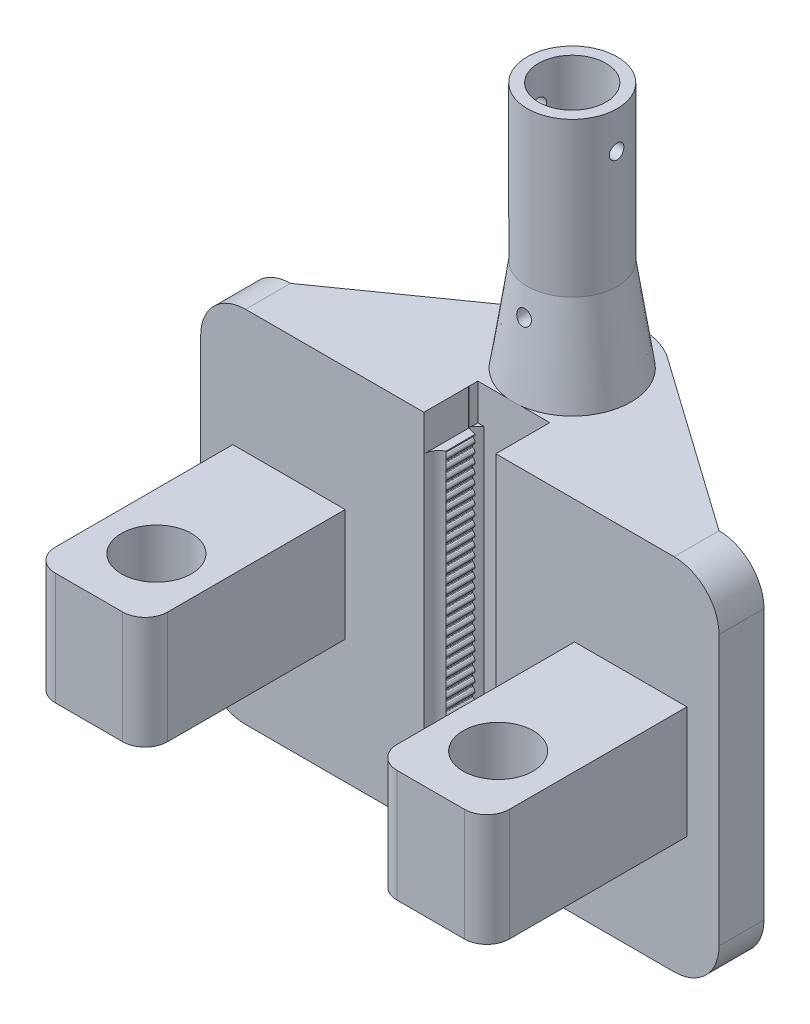
SolidWorks part; units mm, degrees
ref_plane "Piano frontale" through (0, 0, 0) normal (0, 0, 1) x (1, 0, 0)
ref_plane "Piano superiore" through (0, 0, 0) normal (0, 1, 0) x (1, 0, 0)
ref_plane "Piano destro" through (0, 0, 0) normal (1, 0, 0) x (0, 0, -1)
sketch "Schizzo1" plane through (0, 0, 0) normal (0, 0, 1) x (1, 0, 0)
  line L1 (-57.665, 40) -> (57.665, 40)
  line L2 (-57.665, 40) -> (-57.665, -40)
  line L3 (-57.665, -40) -> (57.665, -40)
  line L4 (57.665, 40) -> (57.665, -40)
  line L5 (-57.665, 40) -> (57.665, -40) construction
  line L6 (-57.665, -40) -> (57.665, 40) construction
  point P0 (0, 0)
  dimension "D1" = 80
  dimension "D2" = 115.33
extrude "Estrusione-Estrusione1" add sketch "Schizzo1" along normal blind 10
fillet "Raccordo1" radius 10 4 edges at (-57.665, -40, 5) (57.665, -40, 5) (57.665, 40, 5) (-57.665, 40, 5)
sketch "Schizzo2" plane through (0, 0, 10) normal (0, 0, 1) x (1, 0, 0)
  line L1 (-6.11, 27.5) -> (6.11, 27.5)
  line L2 (-6.11, 27.5) -> (-6.11, -27.5)
  line L3 (-6.11, -27.5) -> (6.11, -27.5)
  line L4 (6.11, 27.5) -> (6.11, -27.5)
  line L5 (-6.11, 27.5) -> (6.11, -27.5) construction
  line L6 (-6.11, -27.5) -> (6.11, 27.5) construction
  point P0 (0, 0)
  dimension "D1" = 55
  dimension "D2" = 12.22
extrude "Estrusione-Estrusione2" add sketch "Schizzo2" against normal blind 5 contours L1 L4 L3 L2
sketch "Schizzo6" plane through (0, 0, 10) normal (0, 0, 1) x (1, 0, 0)
  line L0 (0, 0) -> (49.9303, 0) construction
  line L2 (-6.11, 21.3859) -> (-6.11, -21.3859)
  line L4 (6.11, 21.3859) -> (6.11, -21.3859)
  line L5 (-6.11, 27.5) -> (6.11, -27.5) construction
  line L6 (-6.11, -27.5) -> (6.11, 27.5) construction
  arc A1 (6.11, -21.3859) -> (-6.11, -21.3859) centre (0, -21.3859) cw
  arc A2 (6.11, 21.3859) -> (-6.11, 21.3859) centre (0, 21.3859) ccw
  point P0 (0, 0)
  dimension "D1" = 12.22
  dimension "D2" = 55
extrude "Taglio-Estrusione6" cut sketch "Schizzo6" against normal blind 7
sketch "Schizzo9" plane through (0, 0, 0) normal (0, 0, -1) x (-1, 0, 0)
  line L0 (0, 0) -> (-26.4048, 0) construction
  line L1 (6.11, 23.4312) -> (6.11, -23.4312)
  line L2 (-6.11, 23.4312) -> (-6.11, -23.4312)
  line L3 (6.11, 23.4312) -> (6.11, 40)
  line L4 (-47.665, 40) -> (47.665, 40) construction
  line L5 (6.11, 40) -> (-6.11, 40)
  line L6 (-6.11, 40) -> (-6.11, 23.4312)
  arc A5 (-6.11, -23.4312) -> (6.11, -23.4312) centre (0, -23.4312) ccw
  point P0 (0, 0)
extrude "Taglio-Estrusione8" cut sketch "Schizzo9" against normal blind 53 contours A5 L1 L3 L5 L6 L2
ref_plane "Piano1" through (0, 95, 0) normal (0, 1, 0) x (1, 0, 0)
sketch "Schizzo14" plane through (0, 95, 0) normal (0, 1, 0) x (1, 0, 0)
  circle A1 centre (0, 15) radius 10
  dimension "D2" = 20
extrude "Estrusione-Estrusione5" add sketch "Schizzo14" against normal blind 135 separate body
ref_plane "Piano2" through (0, 0, 5) normal (0, 0, 1) x (1, 0, 0)
ref_plane "Piano3" through (0, -40, 0) normal (0, 1, 0) x (1, 0, 0)
sketch "Schizzo20" plane through (0, -40, 0) normal (0, 1, 0) x (1, 0, 0)
  line L0 (-13.0862, 15) -> (-13.0862, 0)
  line L1 (-47.665, 0) -> (47.665, 0) construction
  line L2 (-13.0862, 0) -> (13.0862, 0)
  line L3 (13.0862, 0) -> (13.0862, 15)
  arc A0 (13.0862, 15) -> (-13.0862, 15) centre (0, 15) ccw
chamfer "Smusso1" distance 2 angle 15 3 edges at (-6.11, 8.2844, 0) (6.11, 8.2844, 0) (0, -29.5412, 0) first distance on face at (0, 2.2523, 0)
ref_plane "Piano4" through (0, 0, 7) normal (0, 0, 1) x (1, 0, 0)
sketch "Schizzo22" plane through (0, 0, 7) normal (0, 0, 1) x (1, 0, 0)
  line L0 (0, 0) -> (47.566, 0) construction
  line L1 (-8, 23.4312) -> (-8, -23.4312)
  line L2 (8, 23.4312) -> (8, -23.4312)
  line L3 (-8, 23.4312) -> (-8, 40)
  line L4 (47.665, 40) -> (6.11, 40) construction
  line L5 (-8, 40) -> (8, 40)
  line L6 (8, 40) -> (8, 23.4312)
  arc A1 (8, -23.4312) -> (-8, -23.4312) centre (0, -23.4312) cw
extrude "Taglio-Estrusione12" cut sketch "Schizzo22" along normal blind 80 contours L1 A1 L2 L6 L5 L3
chamfer "Smusso2" distance 2 angle 15 3 edges at (-8, 8.2844, 7) (0, -31.4312, 7) (8, 8.2844, 7) first distance on face at (0, 6.5207, 7)
extrude "Estrusione-Estrusione9" add sketch "Schizzo20" along normal blind 8 contours L0 L2 L3 A0
sketch "Schizzo23" plane through (0, -32, 0) normal (0, 1, 0) x (1, 0, 0)
  line L0 (-13.0862, 15) -> (-13.0862, 0)
  line L1 (-13.0862, 0) -> (-8.5862, 0)
  line L2 (-13.0862, 0) -> (13.0862, 0) construction
  line L3 (-8.5862, 0) -> (-6.5862, 2)
  line L4 (-6.5862, 2) -> (6.5862, 2)
  line L5 (6.5862, 2) -> (8.5862, 0)
  line L6 (-13.0862, 0) -> (13.0862, 0) construction
  line L7 (8.5862, 0) -> (13.0862, 0)
  line L8 (13.0862, 0) -> (13.0862, 15)
  arc A0 (13.0862, 15) -> (-13.0862, 15) centre (0, 15) ccw
  dimension "D1" = 4.5
  dimension "D2" = 45
  dimension "D3" = 4.5
  dimension "D4" = 2
extrude "Estrusione-Estrusione10" add sketch "Schizzo23" along normal blind 64
sketch "Schizzo24" plane through (0, 32, 0) normal (0, 1, 0) x (1, 0, 0)
  line L0 (-13.0862, 15) -> (-13.0862, 0)
  line L1 (-13.0862, 0) -> (13.0862, 0)
  line L2 (13.0862, 0) -> (13.0862, 15)
  arc A0 (13.0862, 15) -> (-13.0862, 15) centre (0, 15) ccw
extrude "Estrusione-Estrusione11" add sketch "Schizzo24" along normal blind 8
sketch "Schizzo25" plane through (0, 0, 0) normal (1, 0, 0) x (0, 0, -1)
  line L0 (15, 40) -> (15, 81.458) construction
  line L1 (15, 40) -> (28.0862, 40)
  line L2 (28.0862, 40) -> (25, 60.729)
  line L3 (25, 40) -> (25, 95) construction
  line L4 (25, 60.729) -> (15, 60.729)
  line L5 (15, 60.729) -> (15, 40)
revolve "Rivoluzione6" add sketch "Schizzo25" angle 360 about L0
sketch "Schizzo26" plane through (0, 0, 7) normal (0, 0, 1) x (1, 0, 0)
  line L0 (1.3785, -23.4315) -> (-1.3779, -23.431)
  line L1 (-6.8597, 21.1652) -> (-6.8597, 21.6893)
  line L2 (-6.8571, 15.416) -> (-6.8578, 15.1539)
  line L3 (-6.8575, 23.4312) -> (-6.8581, 23.1691)
  line L4 (-6.8571, 7.4009) -> (-6.8578, 7.1388)
  line L5 (-6.1096, 8.4039) -> (-6.1096, 8.4032) construction
  line L6 (6.8582, 31.7083) -> (-6.8572, 31.7085)
  line L7 (-6.8574, 19.4235) -> (-6.858, 19.6856)
  line L8 (-6.1096, 22.4287) -> (-6.1096, 22.4291) construction
  line L9 (-6.8571, -8.6292) -> (-6.8578, -8.8913)
  line L10 (-6.8574, 11.4084) -> (-6.858, 11.6705)
  line L11 (-6.1096, 22.4291) -> (-6.1096, 22.4287)
  line L12 (-6.1096, 22.4287) -> (-6.1096, 22.4291) construction
  line L13 (6.1099, -9.6321) -> (6.1099, -9.6314) construction
  line L14 (-6.8597, 13.1501) -> (-6.8597, 13.6743)
  line L15 (-6.8571, 15.416) -> (-6.8578, 15.6781)
  line L16 (-6.8597, 17.6818) -> (-6.8597, 17.1576)
  line L17 (-6.8574, 19.4235) -> (-6.858, 19.1614)
  line L18 (-6.1096, 8.4032) -> (-6.1096, 8.4039)
  line L19 (-6.8574, 11.4084) -> (-6.858, 11.1463)
  line L20 (-6.8571, 7.4009) -> (-6.8578, 7.663)
  line L21 (-6.8597, 9.6668) -> (-6.8597, 9.1426)
  line L22 (-6.1096, -7.6262) -> (-6.1096, -7.6269) construction
  line L24 (-6.1096, 6.3983) -> (-6.1096, 6.399) construction
  line L25 (-6.8597, 5.1351) -> (-6.8597, 5.6593)
  line L26 (-6.8574, 3.3934) -> (-6.858, 3.6555)
  line L27 (-6.1096, 6.399) -> (-6.1096, 6.3983)
  line L28 (-6.8574, -4.6217) -> (-6.858, -4.3596)
  line L29 (-6.8597, -2.88) -> (-6.8597, -2.3558)
  line L30 (-6.8571, -0.6141) -> (-6.8578, -0.8762)
  line L31 (-6.8597, 1.6517) -> (-6.8597, 1.1275)
  line L32 (-6.1096, -7.6269) -> (-6.1096, -7.6262)
  line L33 (-6.8574, 3.3934) -> (-6.858, 3.1313)
  line L34 (-6.8574, -4.6217) -> (-6.858, -4.8838)
  line L35 (-6.8571, -8.6292) -> (-6.8578, -8.3671)
  line L36 (-6.8571, -0.6141) -> (-6.8578, -0.352)
  line L37 (-6.8597, -6.3633) -> (-6.8597, -6.8875)
  line L39 (-6.1096, -9.6318) -> (-6.1096, -9.6311) construction
  line L40 (-6.8597, -10.895) -> (-6.8597, -10.3708)
  line L41 (-6.8571, -16.6442) -> (-6.8578, -16.9063)
  line L42 (-6.8574, -12.6367) -> (-6.858, -12.3746)
  line L43 (-6.8574, -20.6518) -> (-6.858, -20.3897)
  line L44 (-6.1096, -9.6311) -> (-6.1096, -9.6318)
  line L45 (-6.8597, -18.9101) -> (-6.8597, -18.3859)
  line L46 (-6.8571, -16.6442) -> (-6.8578, -16.3821)
  line L47 (-6.8597, -14.3784) -> (-6.8597, -14.9026)
  line L48 (-6.8574, -12.6367) -> (-6.858, -12.8988)
  line L51 (-6.8575, 23.4312) -> (-6.8581, 23.6933)
  line L52 (6.1099, 6.398) -> (6.1099, 6.3987) construction
  line L53 (-6.8597, -22.3934) -> (-6.8597, -22.9176)
  line L54 (-6.8574, -20.6518) -> (-6.858, -20.9138)
  line L55 (-6.1578, -23.431) -> (-1.3779, -23.431)
  line L58 (6.1099, -7.6265) -> (6.1099, -7.6272) construction
  line L59 (6.1099, 22.4281) -> (6.1099, 22.4288) construction
  line L60 (6.1099, 22.4281) -> (6.1099, 22.4288) construction
  line L61 (6.1099, 8.4036) -> (6.1099, 8.4029) construction
  line L62 (6.1581, -23.4315) -> (1.3785, -23.4315)
  line L63 (6.8577, -20.6522) -> (6.8583, -20.9143)
  line L64 (6.86, -22.3939) -> (6.86, -22.9181)
  line L66 (6.8577, -12.6372) -> (6.8583, -12.8993)
  line L67 (6.86, -14.3788) -> (6.86, -14.903)
  line L68 (6.8574, -16.6447) -> (6.8581, -16.3826)
  line L69 (6.86, -18.9106) -> (6.86, -18.3864)
  line L70 (6.1099, -9.6314) -> (6.1099, -9.6321)
  line L71 (6.8577, -20.6522) -> (6.8583, -20.3901)
  line L72 (6.8577, -12.6372) -> (6.8583, -12.3751)
  line L73 (6.8574, -16.6447) -> (6.8581, -16.9068)
  line L74 (6.86, -10.8955) -> (6.86, -10.3713)
  line L75 (6.86, -6.3638) -> (6.86, -6.888)
  line L76 (6.8574, -0.6146) -> (6.8581, -0.3525)
  line L77 (6.8574, -8.6296) -> (6.8581, -8.3675)
  line L78 (6.8577, -4.6221) -> (6.8583, -4.8842)
  line L79 (6.8577, 3.3929) -> (6.8583, 3.1308)
  line L80 (6.1099, -7.6272) -> (6.1099, -7.6265)
  line L81 (6.86, 1.6513) -> (6.86, 1.1271)
  line L82 (6.8574, -0.6146) -> (6.8581, -0.8767)
  line L83 (6.86, -2.8805) -> (6.86, -2.3563)
  line L84 (6.8577, -4.6221) -> (6.8583, -4.36)
  line L85 (6.1099, 6.3987) -> (6.1099, 6.398)
  line L86 (6.8577, 3.3929) -> (6.8583, 3.655)
  line L87 (6.86, 5.1346) -> (6.86, 5.6588)
  line L88 (6.86, 9.6663) -> (6.86, 9.1421)
  line L89 (6.8574, 7.4005) -> (6.8581, 7.6625)
  line L90 (6.8577, 11.408) -> (6.8583, 11.1459)
  line L91 (6.1099, 8.4029) -> (6.1099, 8.4036)
  line L92 (6.8577, 19.423) -> (6.8583, 19.1609)
  line L93 (6.86, 17.6814) -> (6.86, 17.1572)
  line L94 (6.8574, 15.4155) -> (6.8581, 15.6776)
  line L95 (6.86, 13.1496) -> (6.86, 13.6738)
  line L96 (6.1099, 22.4288) -> (6.1099, 22.4281)
  line L97 (6.8577, 11.408) -> (6.8583, 11.6701)
  line L98 (6.8574, -8.6296) -> (6.8581, -8.8917)
  line L99 (6.8577, 19.423) -> (6.8583, 19.6851)
  line L100 (6.1099, 24.4337) -> (6.1099, 24.433) construction
  line L101 (6.8574, 7.4005) -> (6.8581, 7.1384)
  line L102 (6.8581, 23.4309) -> (6.8587, 23.1688)
  line L103 (6.8574, 15.4155) -> (6.8581, 15.1534)
  line L104 (6.86, 21.1647) -> (6.86, 21.6889)
  line L105 (6.1099, 24.4337) -> (6.1099, 24.433) construction
  line L110 (6.86, 25.697) -> (6.86, 25.1728)
  line L111 (6.8576, 31.4462) -> (6.8582, 31.7083)
  line L112 (6.8581, 23.4309) -> (6.8587, 23.693)
  line L114 (6.8578, 27.4387) -> (6.8584, 27.1766)
  line L117 (6.1099, 24.433) -> (6.1099, 24.4337)
  line L119 (6.8576, 31.4462) -> (6.8582, 31.1841)
  line L120 (6.8601, 29.1804) -> (6.8601, 29.7045)
  line L121 (6.8578, 27.4387) -> (6.8584, 27.7008)
  line L132 (-6.8571, 27.4388) -> (-6.8577, 27.7009)
  line L133 (-6.8593, 29.1805) -> (-6.8592, 29.7047)
  line L134 (-6.8566, 31.4464) -> (-6.8573, 31.1843)
  line L137 (-6.8571, 27.4388) -> (-6.8578, 27.1767)
  line L139 (-6.8566, 31.4464) -> (-6.8572, 31.7085)
  line L140 (-6.8595, 25.6972) -> (-6.8595, 25.173)
  arc A0 (-6.4213, 21.93) -> (-6.421, 22.9276) centre (-6.6647, 22.4289) ccw
  arc A1 (-6.7298, 21.8372) -> (-6.4213, 21.93) centre (-6.8596, 22.8284) ccw
  arc A2 (-6.7298, 21.8372) -> (-6.8597, 21.6893) centre (-6.7105, 21.6893) ccw
  arc A3 (-6.7287, 23.0208) -> (-6.8581, 23.1691) centre (-6.7089, 23.1687) cw
  arc A4 (-6.7287, 23.0208) -> (-6.421, 22.9276) centre (-6.8609, 22.0301) cw
  arc A5 (-6.7299, 21.0172) -> (-6.8597, 21.1652) centre (-6.7105, 21.1651) cw
  arc A6 (-6.7299, 21.0172) -> (-6.4214, 20.9244) centre (-6.8598, 20.0261) cw
  arc A7 (-6.7286, 19.8338) -> (-6.858, 19.6856) centre (-6.7088, 19.6859) ccw
  arc A8 (-6.7286, 19.8338) -> (-6.4202, 19.9273) centre (-6.8607, 20.8246) ccw
  arc A9 (-6.4214, 20.9244) -> (-6.4202, 19.9273) centre (-6.6648, 20.4256) cw
  arc A10 (-6.7298, 17.0097) -> (-6.8597, 17.1576) centre (-6.7105, 17.1576) cw
  arc A11 (-6.7284, 15.8263) -> (-6.8578, 15.6781) centre (-6.7086, 15.6784) ccw
  arc A12 (-6.7284, 15.8263) -> (-6.42, 15.9198) centre (-6.8606, 16.8171) ccw
  arc A13 (-6.4213, 16.917) -> (-6.42, 15.9198) centre (-6.6647, 16.4181) cw
  arc A14 (-6.7298, 17.0097) -> (-6.4213, 16.917) centre (-6.8596, 16.0186) cw
  arc A15 (-6.7299, 17.8297) -> (-6.8597, 17.6818) centre (-6.7105, 17.6818) ccw
  arc A16 (-6.7299, 17.8297) -> (-6.4214, 17.9225) centre (-6.8598, 18.8208) ccw
  arc A17 (-6.4214, 17.9225) -> (-6.4202, 18.9197) centre (-6.6648, 18.4214) ccw
  arc A18 (-6.7286, 19.0132) -> (-6.4202, 18.9197) centre (-6.8607, 18.0224) cw
  arc A19 (-6.7286, 19.0132) -> (-6.858, 19.1614) centre (-6.7088, 19.161) cw
  arc A20 (-6.7286, 11.8187) -> (-6.858, 11.6705) centre (-6.7088, 11.6709) ccw
  arc A21 (-6.7286, 11.8187) -> (-6.4202, 11.9122) centre (-6.8607, 12.8095) ccw
  arc A22 (-6.4214, 12.9094) -> (-6.4202, 11.9122) centre (-6.6648, 12.4105) cw
  arc A23 (-6.7299, 13.0022) -> (-6.4214, 12.9094) centre (-6.8598, 12.0111) cw
  arc A24 (-6.7299, 13.0022) -> (-6.8597, 13.1501) centre (-6.7105, 13.1501) cw
  arc A25 (-6.7298, 13.8222) -> (-6.4213, 13.915) centre (-6.8596, 14.8133) ccw
  arc A26 (-6.4213, 13.915) -> (-6.42, 14.9121) centre (-6.6647, 14.4138) ccw
  arc A27 (-6.7284, 15.0056) -> (-6.42, 14.9121) centre (-6.8606, 14.0149) cw
  arc A28 (-6.7284, 15.0056) -> (-6.8578, 15.1539) centre (-6.7086, 15.1535) cw
  arc A29 (-6.7298, 13.8222) -> (-6.8597, 13.6743) centre (-6.7105, 13.6743) ccw
  arc A30 (-6.4214, 9.9075) -> (-6.4202, 10.9046) centre (-6.6648, 10.4063) ccw
  arc A31 (-6.7286, 10.9981) -> (-6.4202, 10.9046) centre (-6.8607, 10.0073) cw
  arc A32 (-6.7286, 10.9981) -> (-6.858, 11.1463) centre (-6.7088, 11.146) cw
  arc A33 (-6.7299, 9.8147) -> (-6.4214, 9.9075) centre (-6.8598, 10.8058) ccw
  arc A34 (-6.7299, 9.8147) -> (-6.8597, 9.6668) centre (-6.7105, 9.6668) ccw
  arc A35 (-6.7284, 7.8112) -> (-6.42, 7.9048) centre (-6.8606, 8.802) ccw
  arc A36 (-6.7284, 7.8112) -> (-6.8578, 7.663) centre (-6.7086, 7.6634) ccw
  arc A37 (-6.7298, 8.9947) -> (-6.8597, 9.1426) centre (-6.7105, 9.1426) cw
  arc A38 (-6.7298, 8.9947) -> (-6.4213, 8.9019) centre (-6.8596, 8.0036) cw
  arc A39 (-6.4213, 8.9019) -> (-6.42, 7.9048) centre (-6.6647, 8.403) cw
  arc A40 (-6.4213, 5.8999) -> (-6.42, 6.8971) centre (-6.6647, 6.3988) ccw
  arc A41 (-6.7298, 5.8072) -> (-6.4213, 5.8999) centre (-6.8596, 6.7983) ccw
  arc A42 (-6.7298, 5.8072) -> (-6.8597, 5.6593) centre (-6.7105, 5.6592) ccw
  arc A43 (-6.7284, 6.9906) -> (-6.8578, 7.1388) centre (-6.7086, 7.1385) cw
  arc A44 (-6.7284, 6.9906) -> (-6.42, 6.8971) centre (-6.8606, 5.9998) cw
  arc A45 (-6.7299, 4.9871) -> (-6.8597, 5.1351) centre (-6.7105, 5.135) cw
  arc A46 (-6.7299, 4.9871) -> (-6.4214, 4.8943) centre (-6.8598, 3.996) cw
  arc A47 (-6.7286, 3.8037) -> (-6.858, 3.6555) centre (-6.7088, 3.6558) ccw
  arc A48 (-6.7286, 3.8037) -> (-6.4202, 3.8972) centre (-6.8607, 4.7945) ccw
  arc A49 (-6.4214, 4.8943) -> (-6.4202, 3.8972) centre (-6.6648, 4.3955) cw
  arc A50 (-6.7298, 0.9796) -> (-6.8597, 1.1275) centre (-6.7105, 1.1275) cw
  arc A51 (-6.7284, -0.2038) -> (-6.8578, -0.352) centre (-6.7086, -0.3517) ccw
  arc A52 (-6.7284, -0.2038) -> (-6.42, -0.1103) centre (-6.8606, 0.787) ccw
  arc A53 (-6.4213, 0.8869) -> (-6.42, -0.1103) centre (-6.6647, 0.388) cw
  arc A54 (-6.7298, 0.9796) -> (-6.4213, 0.8869) centre (-6.8596, -0.0115) cw
  arc A55 (-6.7299, 1.7996) -> (-6.8597, 1.6517) centre (-6.7105, 1.6517) ccw
  arc A56 (-6.7299, 1.7996) -> (-6.4214, 1.8924) centre (-6.8598, 2.7907) ccw
  arc A57 (-6.4214, 1.8924) -> (-6.4202, 2.8896) centre (-6.6648, 2.3913) ccw
  arc A58 (-6.7286, 2.9831) -> (-6.4202, 2.8896) centre (-6.8607, 1.9923) cw
  arc A59 (-6.7286, 2.9831) -> (-6.858, 3.1313) centre (-6.7088, 3.1309) cw
  arc A60 (-6.7286, -4.2113) -> (-6.858, -4.3596) centre (-6.7088, -4.3592) ccw
  arc A61 (-6.7286, -4.2113) -> (-6.4202, -4.1179) centre (-6.8607, -3.2206) ccw
  arc A62 (-6.4214, -3.1207) -> (-6.4202, -4.1179) centre (-6.6648, -3.6196) cw
  arc A63 (-6.7299, -3.0279) -> (-6.4214, -3.1207) centre (-6.8598, -4.019) cw
  arc A64 (-6.7299, -3.0279) -> (-6.8597, -2.88) centre (-6.7105, -2.88) cw
  arc A65 (-6.7298, -2.2079) -> (-6.4213, -2.1151) centre (-6.8596, -1.2168) ccw
  arc A66 (-6.4213, -2.1151) -> (-6.42, -1.118) centre (-6.6647, -1.6163) ccw
  arc A67 (-6.7284, -1.0245) -> (-6.42, -1.118) centre (-6.8606, -2.0152) cw
  arc A68 (-6.7284, -1.0245) -> (-6.8578, -0.8762) centre (-6.7086, -0.8766) cw
  arc A69 (-6.7298, -2.2079) -> (-6.8597, -2.3558) centre (-6.7105, -2.3558) ccw
  arc A70 (-6.4214, -6.1226) -> (-6.4202, -5.1255) centre (-6.6648, -5.6238) ccw
  arc A71 (-6.7286, -5.032) -> (-6.4202, -5.1255) centre (-6.8607, -6.0228) cw
  arc A72 (-6.7286, -5.032) -> (-6.858, -4.8838) centre (-6.7088, -4.8841) cw
  arc A73 (-6.7299, -6.2154) -> (-6.4214, -6.1226) centre (-6.8598, -5.2243) ccw
  arc A74 (-6.7299, -6.2154) -> (-6.8597, -6.3633) centre (-6.7105, -6.3633) ccw
  arc A75 (-6.7284, -8.2189) -> (-6.42, -8.1253) centre (-6.8606, -7.2281) ccw
  arc A76 (-6.7284, -8.2189) -> (-6.8578, -8.3671) centre (-6.7086, -8.3667) ccw
  arc A77 (-6.7298, -7.0354) -> (-6.8597, -6.8875) centre (-6.7105, -6.8875) cw
  arc A78 (-6.7298, -7.0354) -> (-6.4213, -7.1282) centre (-6.8596, -8.0265) cw
  arc A79 (-6.4213, -7.1282) -> (-6.42, -8.1253) centre (-6.6647, -7.6271) cw
  arc A80 (-6.4213, -10.1302) -> (-6.42, -9.133) centre (-6.6647, -9.6313) ccw
  arc A81 (-6.7298, -10.2229) -> (-6.4213, -10.1302) centre (-6.8596, -9.2318) ccw
  arc A82 (-6.7298, -10.2229) -> (-6.8597, -10.3708) centre (-6.7105, -10.3709) ccw
  arc A83 (-6.7284, -9.0395) -> (-6.8578, -8.8913) centre (-6.7086, -8.8916) cw
  arc A84 (-6.7284, -9.0395) -> (-6.42, -9.133) centre (-6.8606, -10.0303) cw
  arc A85 (-6.7299, -11.043) -> (-6.8597, -10.895) centre (-6.7105, -10.895) cw
  arc A86 (-6.7299, -11.043) -> (-6.4214, -11.1358) centre (-6.8598, -12.034) cw
  arc A87 (-6.7286, -12.2264) -> (-6.858, -12.3746) centre (-6.7088, -12.3743) ccw
  arc A88 (-6.7286, -12.2264) -> (-6.4202, -12.1329) centre (-6.8607, -11.2356) ccw
  arc A89 (-6.4214, -11.1358) -> (-6.4202, -12.1329) centre (-6.6648, -11.6346) cw
  arc A90 (-6.7298, -15.0505) -> (-6.8597, -14.9026) centre (-6.7105, -14.9026) cw
  arc A91 (-6.7284, -16.2339) -> (-6.8578, -16.3821) centre (-6.7086, -16.3818) ccw
  arc A92 (-6.7284, -16.2339) -> (-6.42, -16.1404) centre (-6.8606, -15.2431) ccw
  arc A93 (-6.4213, -15.1432) -> (-6.42, -16.1404) centre (-6.6647, -15.6421) cw
  arc A94 (-6.7298, -15.0505) -> (-6.4213, -15.1432) centre (-6.8596, -16.0416) cw
  arc A95 (-6.7299, -14.2305) -> (-6.8597, -14.3784) centre (-6.7105, -14.3784) ccw
  arc A96 (-6.7299, -14.2305) -> (-6.4214, -14.1377) centre (-6.8598, -13.2394) ccw
  arc A97 (-6.4214, -14.1377) -> (-6.4202, -13.1405) centre (-6.6648, -13.6388) ccw
  arc A98 (-6.7286, -13.047) -> (-6.4202, -13.1405) centre (-6.8607, -14.0378) cw
  arc A99 (-6.7286, -13.047) -> (-6.858, -12.8988) centre (-6.7088, -12.8991) cw
  arc A100 (-6.7286, -20.2414) -> (-6.858, -20.3897) centre (-6.7088, -20.3893) ccw
  arc A101 (-6.7286, -20.2414) -> (-6.4202, -20.1479) centre (-6.8607, -19.2506) ccw
  arc A102 (-6.4214, -19.1508) -> (-6.4202, -20.1479) centre (-6.6648, -19.6496) cw
  arc A103 (-6.7299, -19.058) -> (-6.4214, -19.1508) centre (-6.8598, -20.0491) cw
  arc A104 (-6.7299, -19.058) -> (-6.8597, -18.9101) centre (-6.7105, -18.9101) cw
  arc A105 (-6.7298, -18.238) -> (-6.4213, -18.1452) centre (-6.8596, -17.2469) ccw
  arc A106 (-6.4213, -18.1452) -> (-6.42, -17.1481) centre (-6.6647, -17.6464) ccw
  arc A107 (-6.7284, -17.0545) -> (-6.42, -17.1481) centre (-6.8606, -18.0453) cw
  arc A108 (-6.7284, -17.0545) -> (-6.8578, -16.9063) centre (-6.7086, -16.9067) cw
  arc A109 (-6.7298, -18.238) -> (-6.8597, -18.3859) centre (-6.7105, -18.3859) ccw
  arc A110 (-6.4212, 24.9323) -> (-6.421, 23.9347) centre (-6.6646, 24.4334) cw
  arc A111 (-6.7286, 23.8415) -> (-6.8581, 23.6933) centre (-6.7089, 23.6936) ccw
  arc A112 (6.7289, -21.0625) -> (6.8583, -20.9143) centre (6.7091, -20.9147) ccw
  arc A113 (-6.4213, -23.1583) -> (-6.1578, -23.431) centre (-6.6647, -23.6571) cw
  arc A114 (-6.7298, -23.0655) -> (-6.4213, -23.1583) centre (-6.8596, -24.0566) cw
  arc A115 (-6.7298, -23.0655) -> (-6.8597, -22.9176) centre (-6.7105, -22.9176) cw
  arc A116 (-6.7299, -22.2455) -> (-6.8597, -22.3934) centre (-6.7105, -22.3934) ccw
  arc A117 (-6.7299, -22.2455) -> (-6.4214, -22.1527) centre (-6.8598, -21.2544) ccw
  arc A118 (-6.4214, -22.1527) -> (-6.4202, -21.1556) centre (-6.6648, -21.6539) ccw
  arc A119 (-6.7286, -21.0621) -> (-6.4202, -21.1556) centre (-6.8607, -22.0529) cw
  arc A120 (-6.7286, -21.0621) -> (-6.858, -20.9138) centre (-6.7088, -20.9142) cw
  arc A121 (6.7289, -21.0625) -> (6.4205, -21.156) centre (6.861, -22.0533) ccw
  arc A122 (6.4217, -22.1532) -> (6.4205, -21.156) centre (6.6651, -21.6543) cw
  arc A123 (6.7302, -22.246) -> (6.4217, -22.1532) centre (6.8601, -21.2549) cw
  arc A124 (6.7302, -22.246) -> (6.86, -22.3939) centre (6.7108, -22.3939) cw
  arc A125 (6.7301, -23.066) -> (6.86, -22.9181) centre (6.7108, -22.9181) ccw
  arc A126 (6.7301, -23.066) -> (6.4216, -23.1587) centre (6.8599, -24.0571) ccw
  arc A127 (6.4216, -23.1587) -> (6.1581, -23.4315) centre (6.665, -23.6576) ccw
  arc A128 (6.7301, -18.2385) -> (6.86, -18.3864) centre (6.7108, -18.3864) cw
  arc A129 (6.7287, -17.055) -> (6.8581, -16.9068) centre (6.7089, -16.9072) ccw
  arc A130 (6.7287, -17.055) -> (6.4203, -17.1486) centre (6.8609, -18.0458) ccw
  arc A131 (6.4216, -18.1457) -> (6.4203, -17.1486) centre (6.665, -17.6468) cw
  arc A132 (6.7301, -18.2385) -> (6.4216, -18.1457) centre (6.8599, -17.2473) cw
  arc A133 (6.7302, -19.0585) -> (6.86, -18.9106) centre (6.7108, -18.9106) ccw
  arc A134 (6.7302, -19.0585) -> (6.4217, -19.1513) centre (6.8601, -20.0496) ccw
  arc A135 (6.4217, -19.1513) -> (6.4205, -20.1484) centre (6.6651, -19.6501) ccw
  arc A136 (6.7289, -20.2419) -> (6.4205, -20.1484) centre (6.861, -19.2511) cw
  arc A137 (6.7289, -20.2419) -> (6.8583, -20.3901) centre (6.7091, -20.3898) cw
  arc A138 (6.7289, -13.0475) -> (6.8583, -12.8993) centre (6.7091, -12.8996) ccw
  arc A139 (6.7289, -13.0475) -> (6.4205, -13.141) centre (6.861, -14.0383) ccw
  arc A140 (6.4217, -14.1381) -> (6.4205, -13.141) centre (6.6651, -13.6393) cw
  arc A141 (6.7302, -14.2309) -> (6.4217, -14.1381) centre (6.8601, -13.2398) cw
  arc A142 (6.7302, -14.2309) -> (6.86, -14.3788) centre (6.7108, -14.3788) cw
  arc A143 (6.7301, -15.0509) -> (6.4216, -15.1437) centre (6.8599, -16.042) ccw
  arc A144 (6.4216, -15.1437) -> (6.4203, -16.1408) centre (6.665, -15.6426) ccw
  arc A145 (6.7287, -16.2344) -> (6.4203, -16.1408) centre (6.8609, -15.2436) cw
  arc A146 (6.7287, -16.2344) -> (6.8581, -16.3826) centre (6.7089, -16.3822) cw
  arc A147 (6.7301, -15.0509) -> (6.86, -14.903) centre (6.7108, -14.903) ccw
  arc A148 (6.4217, -11.1362) -> (6.4205, -12.1334) centre (6.6651, -11.6351) ccw
  arc A149 (6.7289, -12.2269) -> (6.4205, -12.1334) centre (6.861, -11.2361) cw
  arc A150 (6.7289, -12.2269) -> (6.8583, -12.3751) centre (6.7091, -12.3747) cw
  arc A151 (6.7302, -11.0434) -> (6.4217, -11.1362) centre (6.8601, -12.0345) ccw
  arc A152 (6.7302, -11.0434) -> (6.86, -10.8955) centre (6.7108, -10.8955) ccw
  arc A153 (6.7287, -9.04) -> (6.4203, -9.1335) centre (6.8609, -10.0307) ccw
  arc A154 (6.7287, -9.04) -> (6.8581, -8.8917) centre (6.7089, -8.8921) ccw
  arc A155 (6.7301, -10.2234) -> (6.86, -10.3713) centre (6.7108, -10.3713) cw
  arc A156 (6.7301, -10.2234) -> (6.4216, -10.1307) centre (6.8599, -9.2323) cw
  arc A157 (6.4216, -10.1307) -> (6.4203, -9.1335) centre (6.665, -9.6318) cw
  arc A158 (6.4216, -7.1286) -> (6.4203, -8.1258) centre (6.665, -7.6275) ccw
  arc A159 (6.7301, -7.0359) -> (6.4216, -7.1286) centre (6.8599, -8.027) ccw
  arc A160 (6.7301, -7.0359) -> (6.86, -6.888) centre (6.7108, -6.888) ccw
  arc A161 (6.7287, -8.2193) -> (6.8581, -8.3675) centre (6.7089, -8.3672) cw
  arc A162 (6.7287, -8.2193) -> (6.4203, -8.1258) centre (6.8609, -7.2285) cw
  arc A163 (6.7302, -6.2159) -> (6.86, -6.3638) centre (6.7108, -6.3638) cw
  arc A164 (6.7302, -6.2159) -> (6.4217, -6.1231) centre (6.8601, -5.2248) cw
  arc A165 (6.7289, -5.0324) -> (6.8583, -4.8842) centre (6.7091, -4.8846) ccw
  arc A166 (6.7289, -5.0324) -> (6.4205, -5.1259) centre (6.861, -6.0232) ccw
  arc A167 (6.4217, -6.1231) -> (6.4205, -5.1259) centre (6.6651, -5.6242) cw
  arc A168 (6.7301, -2.2084) -> (6.86, -2.3563) centre (6.7108, -2.3563) cw
  arc A169 (6.7287, -1.0249) -> (6.8581, -0.8767) centre (6.7089, -0.8771) ccw
  arc A170 (6.7287, -1.0249) -> (6.4203, -1.1185) centre (6.8609, -2.0157) ccw
  arc A171 (6.4216, -2.1156) -> (6.4203, -1.1185) centre (6.665, -1.6167) cw
  arc A172 (6.7301, -2.2084) -> (6.4216, -2.1156) centre (6.8599, -1.2172) cw
  arc A173 (6.7302, -3.0284) -> (6.86, -2.8805) centre (6.7108, -2.8805) ccw
  arc A174 (6.7302, -3.0284) -> (6.4217, -3.1212) centre (6.8601, -4.0195) ccw
  arc A175 (6.4217, -3.1212) -> (6.4205, -4.1183) centre (6.6651, -3.62) ccw
  arc A176 (6.7289, -4.2118) -> (6.4205, -4.1183) centre (6.861, -3.221) cw
  arc A177 (6.7289, -4.2118) -> (6.8583, -4.36) centre (6.7091, -4.3597) cw
  arc A178 (6.7289, 2.9826) -> (6.8583, 3.1308) centre (6.7091, 3.1305) ccw
  arc A179 (6.7289, 2.9826) -> (6.4205, 2.8891) centre (6.861, 1.9918) ccw
  arc A180 (6.4217, 1.892) -> (6.4205, 2.8891) centre (6.6651, 2.3908) cw
  arc A181 (6.7302, 1.7992) -> (6.4217, 1.892) centre (6.8601, 2.7903) cw
  arc A182 (6.7302, 1.7992) -> (6.86, 1.6513) centre (6.7108, 1.6513) cw
  arc A183 (6.7301, 0.9792) -> (6.4216, 0.8864) centre (6.8599, -0.0119) ccw
  arc A184 (6.4216, 0.8864) -> (6.4203, -0.1107) centre (6.665, 0.3875) ccw
  arc A185 (6.7287, -0.2043) -> (6.4203, -0.1107) centre (6.8609, 0.7865) cw
  arc A186 (6.7287, -0.2043) -> (6.8581, -0.3525) centre (6.7089, -0.3521) cw
  arc A187 (6.7301, 0.9792) -> (6.86, 1.1271) centre (6.7108, 1.1271) ccw
  arc A188 (6.4217, 4.8939) -> (6.4205, 3.8967) centre (6.6651, 4.395) ccw
  arc A189 (6.7289, 3.8032) -> (6.4205, 3.8967) centre (6.861, 4.794) cw
  arc A190 (6.7289, 3.8032) -> (6.8583, 3.655) centre (6.7091, 3.6554) cw
  arc A191 (6.7302, 4.9867) -> (6.4217, 4.8939) centre (6.8601, 3.9956) ccw
  arc A192 (6.7302, 4.9867) -> (6.86, 5.1346) centre (6.7108, 5.1346) ccw
  arc A193 (6.7287, 6.9901) -> (6.4203, 6.8966) centre (6.8609, 5.9993) ccw
  arc A194 (6.7287, 6.9901) -> (6.8581, 7.1384) centre (6.7089, 7.138) ccw
  arc A195 (6.7301, 5.8067) -> (6.86, 5.6588) centre (6.7108, 5.6588) cw
  arc A196 (6.7301, 5.8067) -> (6.4216, 5.8994) centre (6.8599, 6.7978) cw
  arc A197 (6.4216, 5.8994) -> (6.4203, 6.8966) centre (6.665, 6.3983) cw
  arc A198 (6.4216, 8.9015) -> (6.4203, 7.9043) centre (6.665, 8.4026) ccw
  arc A199 (6.7301, 8.9942) -> (6.4216, 8.9015) centre (6.8599, 8.0031) ccw
  arc A200 (6.7301, 8.9942) -> (6.86, 9.1421) centre (6.7108, 9.1421) ccw
  arc A201 (6.7287, 7.8108) -> (6.8581, 7.6625) centre (6.7089, 7.6629) cw
  arc A202 (6.7287, 7.8108) -> (6.4203, 7.9043) centre (6.8609, 8.8016) cw
  arc A203 (6.7302, 9.8142) -> (6.86, 9.6663) centre (6.7108, 9.6663) cw
  arc A204 (6.7302, 9.8142) -> (6.4217, 9.907) centre (6.8601, 10.8053) cw
  arc A205 (6.7289, 10.9977) -> (6.8583, 11.1459) centre (6.7091, 11.1455) ccw
  arc A206 (6.7289, 10.9977) -> (6.4205, 10.9042) centre (6.861, 10.0069) ccw
  arc A207 (6.4217, 9.907) -> (6.4205, 10.9042) centre (6.6651, 10.4059) cw
  arc A208 (6.7301, 13.8217) -> (6.86, 13.6738) centre (6.7108, 13.6738) cw
  arc A209 (6.7287, 15.0052) -> (6.8581, 15.1534) centre (6.7089, 15.153) ccw
  arc A210 (6.7287, 15.0052) -> (6.4203, 14.9116) centre (6.8609, 14.0144) ccw
  arc A211 (6.4216, 13.9145) -> (6.4203, 14.9116) centre (6.665, 14.4134) cw
  arc A212 (6.7301, 13.8217) -> (6.4216, 13.9145) centre (6.8599, 14.8128) cw
  arc A213 (6.7302, 13.0017) -> (6.86, 13.1496) centre (6.7108, 13.1496) ccw
  arc A214 (6.7302, 13.0017) -> (6.4217, 12.9089) centre (6.8601, 12.0106) ccw
  arc A215 (6.4217, 12.9089) -> (6.4205, 11.9118) centre (6.6651, 12.4101) ccw
  arc A216 (6.7289, 11.8183) -> (6.4205, 11.9118) centre (6.861, 12.8091) cw
  arc A217 (6.7289, 11.8183) -> (6.8583, 11.6701) centre (6.7091, 11.6704) cw
  arc A218 (6.7289, 19.0127) -> (6.8583, 19.1609) centre (6.7091, 19.1606) ccw
  arc A219 (6.7289, 19.0127) -> (6.4205, 18.9192) centre (6.861, 18.0219) ccw
  arc A220 (6.4217, 17.9221) -> (6.4205, 18.9192) centre (6.6651, 18.4209) cw
  arc A221 (6.7302, 17.8293) -> (6.4217, 17.9221) centre (6.8601, 18.8204) cw
  arc A222 (6.7302, 17.8293) -> (6.86, 17.6814) centre (6.7108, 17.6814) cw
  arc A223 (6.7301, 17.0093) -> (6.4216, 16.9165) centre (6.8599, 16.0182) ccw
  arc A224 (6.4216, 16.9165) -> (6.4203, 15.9194) centre (6.665, 16.4176) ccw
  arc A225 (6.7287, 15.8258) -> (6.4203, 15.9194) centre (6.8609, 16.8166) cw
  arc A226 (6.7287, 15.8258) -> (6.8581, 15.6776) centre (6.7089, 15.678) cw
  arc A227 (6.7301, 17.0093) -> (6.86, 17.1572) centre (6.7108, 17.1572) ccw
  arc A228 (6.4217, 20.924) -> (6.4205, 19.9268) centre (6.6651, 20.4251) ccw
  arc A229 (6.7289, 19.8333) -> (6.4205, 19.9268) centre (6.861, 20.8241) cw
  arc A230 (6.7289, 19.8333) -> (6.8583, 19.6851) centre (6.7091, 19.6855) cw
  arc A231 (6.7302, 21.0168) -> (6.4217, 20.924) centre (6.8601, 20.0257) ccw
  arc A232 (6.7302, 21.0168) -> (6.86, 21.1647) centre (6.7108, 21.1647) ccw
  arc A233 (6.7293, 23.0205) -> (6.421, 22.927) centre (6.8615, 22.0298) ccw
  arc A234 (6.7293, 23.0205) -> (6.8587, 23.1688) centre (6.7095, 23.1684) ccw
  arc A235 (6.7301, 21.8368) -> (6.86, 21.6889) centre (6.7108, 21.6889) cw
  arc A236 (6.7301, 21.8368) -> (6.4216, 21.9295) centre (6.8599, 22.8279) cw
  arc A237 (6.4216, 21.9295) -> (6.421, 22.927) centre (6.665, 22.4284) cw
  arc A238 (-6.7286, 23.8415) -> (-6.421, 23.9347) centre (-6.8608, 24.8323) ccw
  arc A244 (6.4216, 24.9322) -> (6.421, 23.9347) centre (6.665, 24.4333) ccw
  arc A245 (6.7302, 25.0249) -> (6.4216, 24.9322) centre (6.8599, 24.0338) ccw
  arc A246 (6.7302, 25.0249) -> (6.86, 25.1728) centre (6.7108, 25.1728) ccw
  arc A247 (6.7293, 23.8412) -> (6.8587, 23.693) centre (6.7096, 23.6933) cw
  arc A248 (6.7293, 23.8412) -> (6.421, 23.9347) centre (6.8615, 24.832) cw
  arc A249 (6.7302, 25.8449) -> (6.86, 25.697) centre (6.7109, 25.697) cw
  arc A250 (6.7302, 25.8449) -> (6.4217, 25.9377) centre (6.8601, 26.836) cw
  arc A251 (6.7289, 27.0284) -> (6.8584, 27.1766) centre (6.7092, 27.1762) ccw
  arc A252 (6.7289, 27.0284) -> (6.4206, 26.9349) centre (6.861, 26.0376) ccw
  arc A253 (6.4217, 25.9377) -> (6.4206, 26.9349) centre (6.6652, 26.4366) cw
  arc A254 (6.7302, 29.8524) -> (6.8601, 29.7045) centre (6.7109, 29.7045) cw
  arc A255 (6.7288, 31.0359) -> (6.8582, 31.1841) centre (6.709, 31.1838) ccw
  arc A256 (6.7288, 31.0359) -> (6.4205, 30.9424) centre (6.861, 30.0451) ccw
  arc A257 (6.4217, 29.9452) -> (6.4205, 30.9424) centre (6.6651, 30.4441) cw
  arc A258 (6.7302, 29.8524) -> (6.4217, 29.9452) centre (6.86, 30.8436) cw
  arc A259 (6.7303, 29.0324) -> (6.8601, 29.1804) centre (6.7109, 29.1803) ccw
  arc A260 (6.7303, 29.0324) -> (6.4217, 28.9396) centre (6.8601, 28.0413) ccw
  arc A261 (6.4217, 28.9396) -> (6.4206, 27.9425) centre (6.6652, 28.4408) ccw
  arc A262 (6.7289, 27.849) -> (6.4206, 27.9425) centre (6.8611, 28.8398) cw
  arc A263 (6.7289, 27.849) -> (6.8584, 27.7008) centre (6.7092, 27.7011) cw
  arc A321 (-6.7283, 27.8491) -> (-6.8577, 27.7009) centre (-6.7086, 27.7013) ccw
  arc A322 (-6.7283, 27.8491) -> (-6.4199, 27.9426) centre (-6.8603, 28.84) ccw
  arc A323 (-6.421, 28.9398) -> (-6.4199, 27.9426) centre (-6.6645, 28.4409) cw
  arc A324 (-6.7295, 29.0326) -> (-6.421, 28.9398) centre (-6.8595, 28.0415) cw
  arc A325 (-6.7295, 29.0326) -> (-6.8593, 29.1805) centre (-6.7101, 29.1805) cw
  arc A326 (-6.7294, 29.8526) -> (-6.4209, 29.9453) centre (-6.8591, 30.8437) ccw
  arc A327 (-6.4209, 29.9453) -> (-6.4195, 30.9425) centre (-6.6642, 30.4442) ccw
  arc A328 (-6.7279, 31.036) -> (-6.4195, 30.9425) centre (-6.8602, 30.0453) cw
  arc A329 (-6.7279, 31.036) -> (-6.8573, 31.1843) centre (-6.7081, 31.1839) cw
  arc A330 (-6.7294, 29.8526) -> (-6.8592, 29.7047) centre (-6.7101, 29.7047) ccw
  arc A331 (-6.4212, 25.9379) -> (-6.42, 26.935) centre (-6.6646, 26.4367) ccw
  arc A332 (-6.7283, 27.0285) -> (-6.42, 26.935) centre (-6.8605, 26.0377) cw
  arc A333 (-6.7283, 27.0285) -> (-6.8578, 27.1767) centre (-6.7086, 27.1764) cw
  arc A334 (-6.7297, 25.8451) -> (-6.4212, 25.9379) centre (-6.8595, 26.8362) ccw
  arc A335 (-6.7297, 25.8451) -> (-6.8595, 25.6972) centre (-6.7104, 25.6972) ccw
  arc A336 (-6.7297, 25.0251) -> (-6.8595, 25.173) centre (-6.7104, 25.173) cw
  arc A337 (-6.7297, 25.0251) -> (-6.4212, 24.9323) centre (-6.8595, 24.034) cw
  point P24 (-6.8597, 21.4273)
  point P109 (-6.8597, 9.4049)
  point P204 (-6.8597, 5.3973)
  point P205 (-6.8597, -6.6252)
  point P278 (-6.8597, -10.6328)
  point P587 (6.86, -10.6331)
  point P588 (6.86, -6.6255)
  point P589 (6.86, 5.397)
  point P590 (6.86, 9.4046)
  point P591 (6.86, 21.4268)
  point P806 (6.86, 25.4349)
  point P807 (6.8602, 37.4571)
  point P832 (-6.8588, 37.4575)
  point P833 (-6.8595, 25.4351)
extrude "Taglio-Estrusione14" cut sketch "Schizzo26" against normal blind 8 contours L3 A3 A4 A0 A1 A2 L1 A5 A6 A9 A8 A7 L7 L17 A19 A18 A17 A16 A15 L16 A10 A14 A13 A12 A11 L15 L2 A28 A27 A26 A25 A29 L14 A24 A23 A22 A21 A20 L10 L19 A32 A31 A30 A33 A34 L21 A37 A38 A39 A35 A36 L20 L4 A43 A44 A40 A41 A42 L25 A45 A46 A49 A48 A47 L26 L33 A59 A58 A57 A56 A55 L31 A50 A54 A53 A52 A51 L36 L30 A68 A67 A66 A65 A69 L29 A64 A63 A62 A61 A60 L28 L34 A72 A71 A70 A73 A74 L37 A77 A78 A79 A75 A76 L35 L9 A83 A84 A80 A81 A82 L40 A85 A86 A89 A88 A87 L42 L48 A99 A98 A97 A96 A95 L47 A90 A94 A93 A92 A91 L46 L41 A108 A107 A106 A105 A109 L45 A104 A103 A102 A101 A100 L43 L54 A120 A119 A118 A117 A116 L53 A115 A114 A113 L55 L0 L62 A127 A126 A125 L64 A124 A123 A122 A121 A112 L63 L71 A137 A136 A135 A134 A133 L69 A128 A132 A131 A130 A129 L73 L68 A146 A145 A144 A143 A147 L67 A142 A141 A140 A139 A138 L66 L72 A150 A149 A148 A151 A152 L74 A155 A156 A157 A153 A154 L98 L77 A161 A162 A158 A159 A160 L75 A163 A164 A167 A166 A165 L78 L84 A177 A176 A175 A174 A173 L83 A168 A172 A171 A170 A169 L82 L76 A186 A185 A184 A183 A187 L81 A182 A181 A180 A179 A178 L79 L86 A190 A189 A188 A191 A192 L87 A195 A196 A197 A193 A194 L101 L89 A201 A202 A198 A199 A200 L88 A203 A204 A207 A206 A205 L90 L97 A217 A216 A215 A214 A213 L95 A208 A212 A211 A210 A209 L103 L94 A226 A225 A224 A223 A227 L93 A222 A221 A220 A219 A218 L92 L99 A230 A229 A228 A231 A232 L104 A235 A236 A237 A233 A234 L102 L112 A247 A248 A244 A245 A246 L110 A249 A250 A253 A252 A251 L114 L121 A263 A262 A261 A260 A259 L120 A254 A258 A257 A256 A255 L119 L111 L6 L139 L134 A329 A328 A327 A326 A330 L133 A325 A324 A323 A322 A321 L132 L137 A333 A332 A331 A334 A335 L140 A336 A337 A110 A238 A111 L51
sketch "Schizzo32" plane through (0, 0, 10) normal (0, 0, 1) x (1, 0, 0)
  line L0 (0, 0) -> (-65.759, 0) construction
  line L2 (-25.52, 12.5) -> (-50.52, 12.5)
  line L3 (-25.52, 12.5) -> (-25.52, -12.5)
  line L4 (-25.52, -12.5) -> (-50.52, -12.5)
  line L5 (-50.52, 12.5) -> (-50.52, -12.5)
  line L6 (-25.52, 12.5) -> (-50.52, -12.5) construction
  line L7 (-25.52, -12.5) -> (-50.52, 12.5) construction
  line L8 (-57.665, 30) -> (-57.665, -30) construction
  point P3 (-38.02, 0)
  dimension "D1" = 25
  dimension "D2" = 25
  dimension "D3" = 19.645
extrude "Estrusione-Estrusione13" add sketch "Schizzo32" along normal blind 44.5 contours L5 L4 L3 L2
fillet "Raccordo7" radius 5 2 edges at (-25.52, 0, 54.5) (-50.52, 0, 54.5)
sketch "Schizzo33" plane through (0, 12.5, 0) normal (0, 1, 0) x (1, 0, 0)
  line L0 (-38.02, -54.5) -> (-38.02, -19.6568) construction
  line L1 (-30.52, -54.5) -> (-45.52, -54.5) construction
  circle A0 centre (-38.02, -39.5) radius 7.8
  dimension "D1" = 15
  dimension "D2" = 15.6
extrude "Taglio-Estrusione16" cut sketch "Schizzo33" against normal blind 35
mirror "Specchia1" about plane through (0, 0, 0) normal (1, 0, 0) of "Raccordo7", "Taglio-Estrusione16", "Estrusione-Estrusione13"
sketch "Schizzo35" plane through (0, 95, 0) normal (0, 1, 0) x (1, 0, 0)
  circle A0 centre (0, 15) radius 7.5
extrude "Taglio-Estrusione17" cut sketch "Schizzo35" against normal blind 47.44 contours A0
ref_plane "Piano6" through (0, 55, 0) normal (0, 1, 0) x (1, 0, 0)
sketch "Schizzo36" plane through (0, 0, 0) normal (0, 0, 1) x (1, 0, 0)
  line L1 (0, 95) -> (0, 14.6353) construction
  line L2 (10, 95) -> (-10, 95) construction
  circle A1 centre (0, 55.18) radius 1.62
  dimension "D2" = 3.24
extrude "Taglio-Estrusione18" cut sketch "Schizzo36" against normal blind 45
sketch "Schizzo37" plane through (0, 0, 0) normal (1, 0, 0) x (0, 0, -1)
  line L0 (15, 95) -> (15, 63.0779) construction
  line L1 (25, 95) -> (5, 95) construction
  circle A0 centre (15, 86.7481) radius 1.62
  dimension "D1" = 3.24
  dimension "D2" = 8.2519
extrude "Taglio-Estrusione19" cut sketch "Schizzo37" against normal mid plane 45
sketch "Schizzo38" plane through (0, -40, 0) normal (0, -1, 0) x (1, 0, 0)
  line L0 (47.665, 0) -> (7.9016, -28.0862)
  line L1 (47.665, 0) -> (13.0862, 0)
  line L2 (13.0862, 0) -> (13.0862, -15)
  line L3 (0, -15) -> (0, 45.9188) construction
  line L4 (-13.0862, 0) -> (-13.0862, -15)
  line L5 (-47.665, 0) -> (-13.0862, 0)
  line L6 (-47.665, 0) -> (-7.9016, -28.0862)
  arc A0 (-13.0862, -15) -> (13.0862, -15) centre (0, -15) ccw
  arc A2 (-7.9016, -28.0862) -> (7.9016, -28.0862) centre (0, -15) ccw
extrude "Estrusione-Estrusione14" add sketch "Schizzo38" against normal up to surface (80 mm away) contours L0 A2 L6 L5 L4 A0 L2 L1 up to face at (0, 40, 2.9605)
sketch "Schizzo39" plane through (0, 40, 0) normal (0, 1, 0) x (1, 0, 0)
  line L1 (-8, -10) -> (8, -10)
  line L2 (-8, -10) -> (-8, 2)
  line L3 (-8, 2) -> (8, 2)
  line L4 (8, -10) -> (8, 2)
  dimension "D1" = 12
extrude "Taglio-Estrusione21" cut sketch "Schizzo39" against normal blind 8.05
fillet "Raccordo8" radius 3.2 3 edges at (8, 4.2594, 7.5359) (-8, 4.2594, 7.5359) (0, -31.4312, 7.5359)
